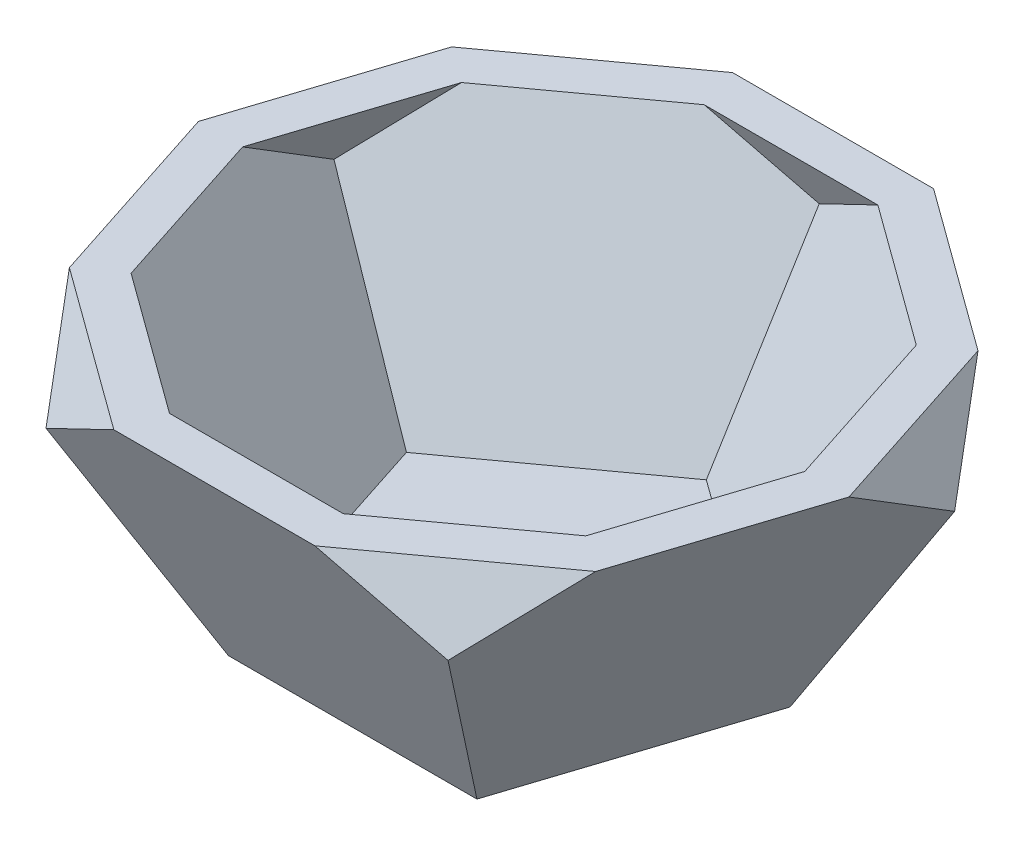
SolidWorks part; units mm, degrees
ref_plane "Front" through (0, 0, 0) normal (0, 0, 1) x (1, 0, 0)
ref_plane "Top" through (0, 0, 0) normal (0, 1, 0) x (1, 0, 0)
ref_plane "Right" through (0, 0, 0) normal (1, 0, 0) x (0, 0, -1)
ref_axis "Center Axis" through (0, 0, -88.99) along (0, 0, 1)
sketch "Sketch1" plane through (0, 0, 0) normal (0, 1, 0) x (1, 0, 0)
  line L0 (-12.0784, 3.9245) -> (12.0784, 3.9245) construction
  line L1 (12.0784, 3.9245) -> (0, 12.7)
  line L2 (0, 12.7) -> (-12.0784, 3.9245)
  line L3 (-12.0784, 3.9245) -> (-7.4649, -10.2745)
  line L4 (-7.4649, -10.2745) -> (7.4649, -10.2745)
  line L5 (7.4649, -10.2745) -> (12.0784, 3.9245)
  circle A0 centre (0, 0) radius 12.7 construction
  dimension "D1" = 25.4
extrude "Boss-Extrude1" add sketch "Sketch1" along normal blind 33.2486 draft 26.565 draft outward yes
sketch "Sketch2" plane through (0, 33.2486, 0) normal (0, 1, 0) x (1, 0, 0)
  line L0 (-7.4649, 10.2745) -> (0, 12.7) construction
  line L1 (7.4649, 10.2745) -> (-7.4649, 10.2745)
  line L2 (-7.4649, 10.2745) -> (-12.0784, -3.9245)
  line L3 (-12.0784, -3.9245) -> (0, -12.7)
  line L4 (0, -12.7) -> (12.0784, -3.9245)
  line L5 (12.0784, -3.9245) -> (7.4649, 10.2745)
  line L6 (0, 12.7) -> (7.4649, 10.2745) construction
  circle A0 centre (0, 0) radius 12.7 construction
  circle A1 centre (0, 0) radius 10.2745 construction
extrude "Cut-Extrude1" cut sketch "Sketch2" against normal blind 33.2486 draft 26.565 flip side to cut
scale "Scale1" bodies to scale 167 scale about origin uniform scaling yes scale factor 1.125
ref_plane "Plane2" through (0, 18.7023, 0) normal (0, 1, 0) x (1, 0, 0)
sketch "Sketch4" plane through (0, 12.1045, -24.2089) normal (0, 0.4472, -0.8944) x (-1, 0, 0)
  line L0 (-13.5881, 12.3128) -> (10.9931, 20.2997) construction
  line L1 (13.5881, 12.3128) -> (8.398, 28.2865) construction
  line L2 (0, 2.4405) -> (0, 28.2865) construction
  line L3 (-8.398, 28.2865) -> (8.398, 28.2865) construction
  circle A0 centre (0, 16.7278) radius 24.13
  dimension "D1" = 48.26
sketch "Sketch3" plane through (0, 18.7023, 0) normal (0, 1, 0) x (1, 0, 0)
  line L1 (-40.0956, 34.6618) -> (53.116, 34.6618)
  line L2 (-40.0956, 34.6618) -> (-40.0956, -34.3243)
  line L3 (-40.0956, -34.3243) -> (53.116, -34.3243)
  line L4 (53.116, 34.6618) -> (53.116, -34.3243)
extrude "Cut-Extrude2" cut sketch "Sketch3" along normal through all
shell "Shell1" thickness 2.54 removed face at (0, 18.7023, 0)
equation "\"Ratio\"= sin ( 18 ) + 1"
equation "\"Height\"= \"D1@Sketch1\" * \"Ratio\""
